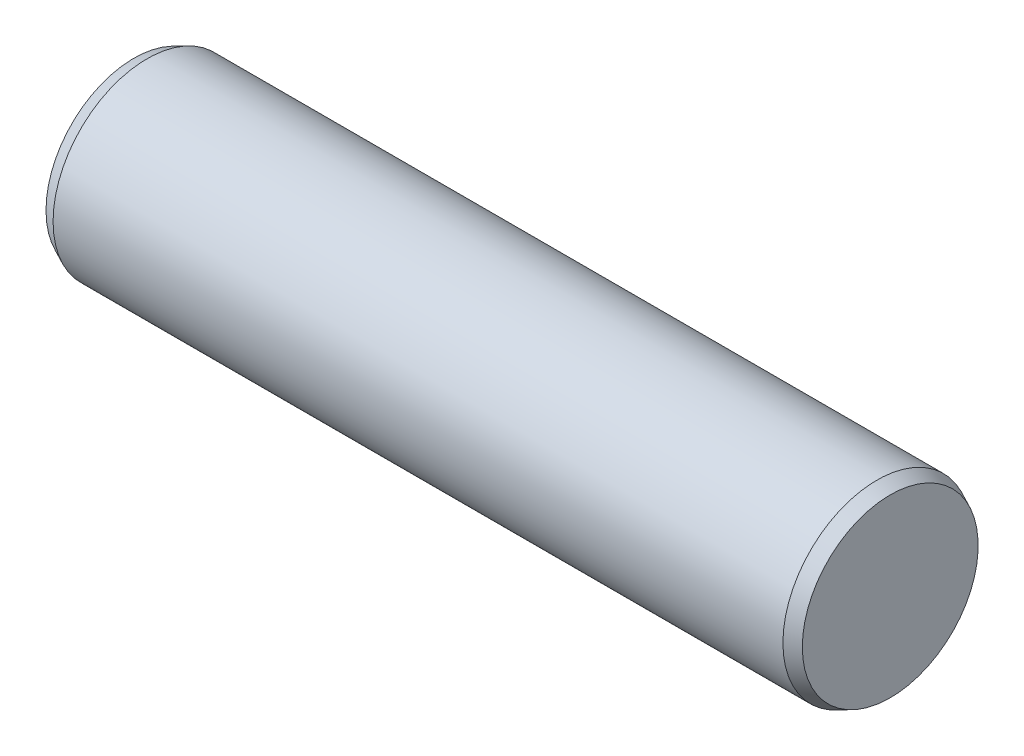
SolidWorks part; units mm, degrees
ref_plane "Plane1" through (0, 0, 0) normal (0, 0, 1) x (1, 0, 0)
ref_plane "Plane2" through (0, 0, 0) normal (0, 1, 0) x (1, 0, 0)
ref_plane "Plane3" through (0, 0, 0) normal (1, 0, 0) x (0, 0, -1)
sketch "Sketch1" plane through (0, 0, 0) normal (0, 0, 1) x (1, 0, 0)
  line L1 (-6.35, 0) -> (107.95, 0) construction
  line L2 (0, 0) -> (101.6, 0)
  line L3 (101.6, 0) -> (101.6, 11.8099)
  line L4 (101.6, 11.8099) -> (99.822, 12.639)
  line L5 (99.822, 12.639) -> (1.778, 12.639)
  line L6 (0, 11.8099) -> (0, 0)
  line L7 (1.778, 12.639) -> (0, 11.8099)
  dimension "D3" = 25
  dimension "Diameter" = 25.2781
  dimension "D1" = 25
  dimension "D2" = 1.778
  dimension "Length" = 101.6
revolve "Base-Revolve" add sketch "Sketch1" angle 360 about L1
equation "\"D2@Sketch1\" = \"Chamfer_length@Sketch1\""
